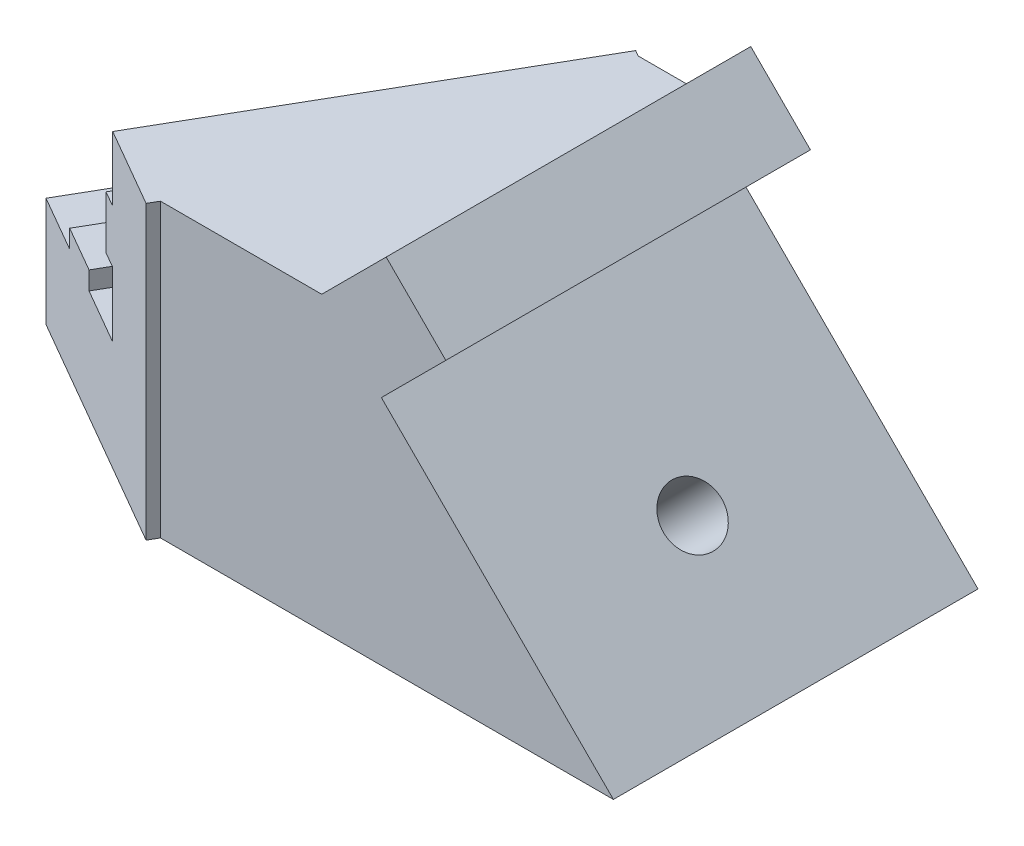
SolidWorks part; units mm, degrees
ref_plane "Front Plane" through (0, 0, 0) normal (0, 0, 1) x (1, 0, 0)
ref_plane "Top Plane" through (0, 0, 0) normal (0, 1, 0) x (1, 0, 0)
ref_plane "Right Plane" through (0, 0, 0) normal (1, 0, 0) x (0, 0, -1)
sketch "Esquisse1" plane through (0, 0, 0) normal (0, 0, 1) x (1, 0, 0)
  line L0 (10, 16) -> (26, 0)
  line L1 (26, 0) -> (0, 0)
  line L2 (0, 0) -> (0, 16)
  line L3 (0, 16) -> (10, 16)
  dimension "D1" = 10
  dimension "D2" = 135
  dimension "D3" = 16
extrude "Boss.-Extru.1" add sketch "Esquisse1" along normal blind 20
sketch "Esquisse2" plane through (13, 13, 0) normal (0.7071, 0.7071, 0) x (0, 0, -1)
  line L0 (-20, -18.3848) -> (0, -18.3848) construction
  line L3 (-20, -18.3848) -> (-20, 4.2426) construction
  circle A0 centre (-10, -10.3848) radius 1.6
  point P7 (-18.3937, -14.2904)
  dimension "D1" = 3.2
  dimension "D2" = 8
  dimension "D3" = 10
extrude "Enlèv. mat.-Extru.1" cut sketch "Esquisse2" against normal through all
ref_plane "Plan1" through (9.4645, 9.4645, 0) normal (0.7071, 0.7071, 0) x (0, 0, -1)
sketch "Esquisse3" plane through (9.4645, 9.4645, 0) normal (0.7071, 0.7071, 0) x (0, 0, -1)
  circle A0 centre (-10, -10.3848) radius 4.25
  circle A1 centre (-10, -10.3848) radius 1.6 construction
  dimension "D1" = 8.5
extrude "Enlèv. mat.-Extru.2" cut sketch "Esquisse3" against normal through all
ref_axis "Axe1" through (9.1001, 9.8288, 0) along (0.7071, -0.7071, 0)
ref_plane "Plan3" through (0, 0, 0) normal (-0.866, 0, -0.5) x (0, -1, 0)
sketch "Esquisse4" plane through (0, 0, 0) normal (-0.866, 0, -0.5) x (0, -1, 0)
  line L1 (4.4994, 17.8157) -> (-17.7877, 17.8157)
  line L2 (4.4994, 17.8157) -> (4.4994, -17.0003)
  line L3 (4.4994, -17.0003) -> (-17.7877, -17.0003)
  line L4 (-17.7877, 17.8157) -> (-17.7877, -17.0003)
extrude "Enlèv. mat.-Extru.3" cut sketch "Esquisse4" against normal blind 6
ref_plane "Plan4" through (1.7321, 0, -3) normal (-0.5, 0, 0.866) x (0, 1, 0)
ref_plane "Plan5" through (0, 0, 12) normal (0.5, 0, -0.866) x (-0.866, 0, -0.5)
ref_plane "Plan6" through (-8.6603, 0, 15) normal (0.5, 0, -0.866) x (-0.866, 0, -0.5)
sketch "Esquisse5" plane through (-3.4641, 0, 18) normal (0.5, 0, -0.866) x (-0.866, 0, -0.5)
  line L0 (-5, 0) -> (10, 0)
  line L1 (10, 0) -> (10, 6)
  line L2 (10, 6) -> (6.45, 6)
  line L3 (6.45, 6) -> (6.45, 7)
  line L4 (6.45, 7) -> (3.55, 7)
  line L5 (3.55, 7) -> (3.55, 6)
  line L6 (3.55, 6) -> (0, 6)
  line L7 (0, 6) -> (0, 9.55)
  line L8 (0, 9.55) -> (1, 9.55)
  line L9 (1, 9.55) -> (1, 12.45)
  line L10 (1, 12.45) -> (0, 12.45)
  line L11 (0, 12.45) -> (0, 16)
  line L12 (0, 16) -> (-5, 16)
  line L13 (-5, 16) -> (-5, 0)
  line L16 (0, 16) -> (0, 0) construction
  dimension "D1" = 10
  dimension "D2" = 2.9
  dimension "D3" = 1
  dimension "D4" = 6
  dimension "D5" = 5
  dimension "D6" = 10
extrude "Boss.-Extru.3" add sketch "Esquisse5" along normal blind 21
sketch "Esquisse6" plane through (13, 13, 0) normal (0.7071, 0.7071, 0) x (0, 0, -1)
  line L0 (0, -18.3848) -> (0, 4.2426) construction
  line L1 (0, -0.3848) -> (-20, -0.3848)
  line L2 (0, -0.3848) -> (0, 4.2426)
  line L3 (0, 4.2426) -> (-20, 4.2426)
  line L4 (-20, -0.3848) -> (-20, 4.2426)
  line L5 (-20, -18.3848) -> (0, -18.3848) construction
  dimension "D1" = 18
extrude "Boss.-Extru.4" add sketch "Esquisse6" along normal blind 5
sketch "Esquisse7" plane through (0, 7, 0) normal (0, 1, 0) x (1, 0, 0)
  line L2 (1.45, 3.4115) -> (3.9615, 1.9615) construction
  line L3 (3.9615, 1.9615) -> (-6.5385, -16.225) construction
  circle A0 centre (-2.2942, -5.9737) radius 1.6
  point P2 (0, 0)
  point P3 (0, 0)
  dimension "D1" = 3.2
  dimension "D2" = 10
  dimension "D3" = 1.45
extrude "Enlèv. mat.-Extru.4" cut sketch "Esquisse7" against normal through all
